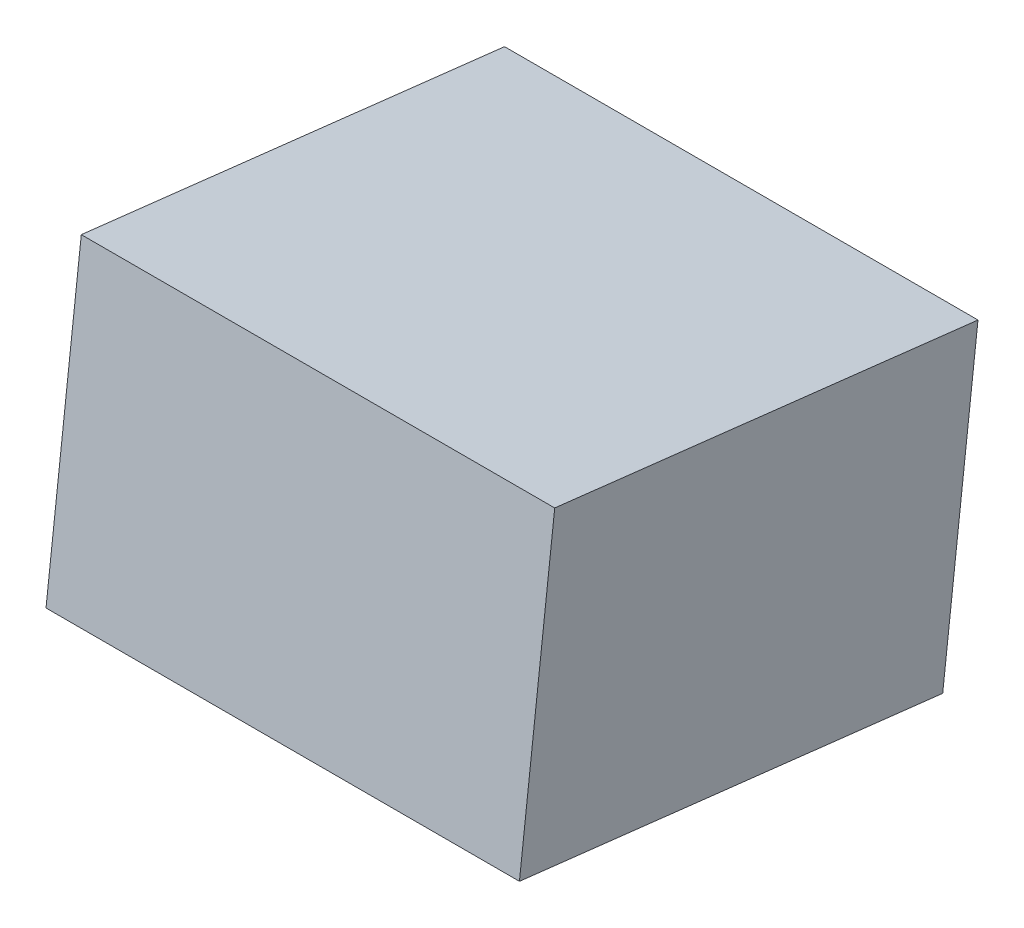
SolidWorks part; units mm, degrees
ref_plane "Front Plane" through (0, 0, 0) normal (0, 0, 1) x (1, 0, 0)
ref_plane "Top Plane" through (0, 0, 0) normal (0, 1, 0) x (1, 0, 0)
ref_plane "Right Plane" through (0, 0, 0) normal (1, 0, 0) x (0, 0, -1)
sketch "Sketch1" plane through (0, 358.8799, -41.4225) normal (0, 0.9934, -0.1147) x (1, 0, 0)
  line L1 (-231.6731, 142.5526) -> (-31.6731, 142.5526)
  line L2 (-231.6731, 142.5526) -> (-231.6731, 322.5526)
  line L3 (-231.6731, 322.5526) -> (-31.6731, 322.5526)
  line L4 (-31.6731, 142.5526) -> (-31.6731, 322.5526)
  line L5 (-231.6731, 142.5526) -> (-31.6731, 322.5526) construction
  line L6 (-231.6731, 322.5526) -> (-31.6731, 142.5526) construction
  point P0 (-131.6731, 232.5526)
  dimension "D1" = 180
  dimension "D2" = 200
extrude "Boss-Extrude1" add sketch "Sketch1" along normal blind 130
